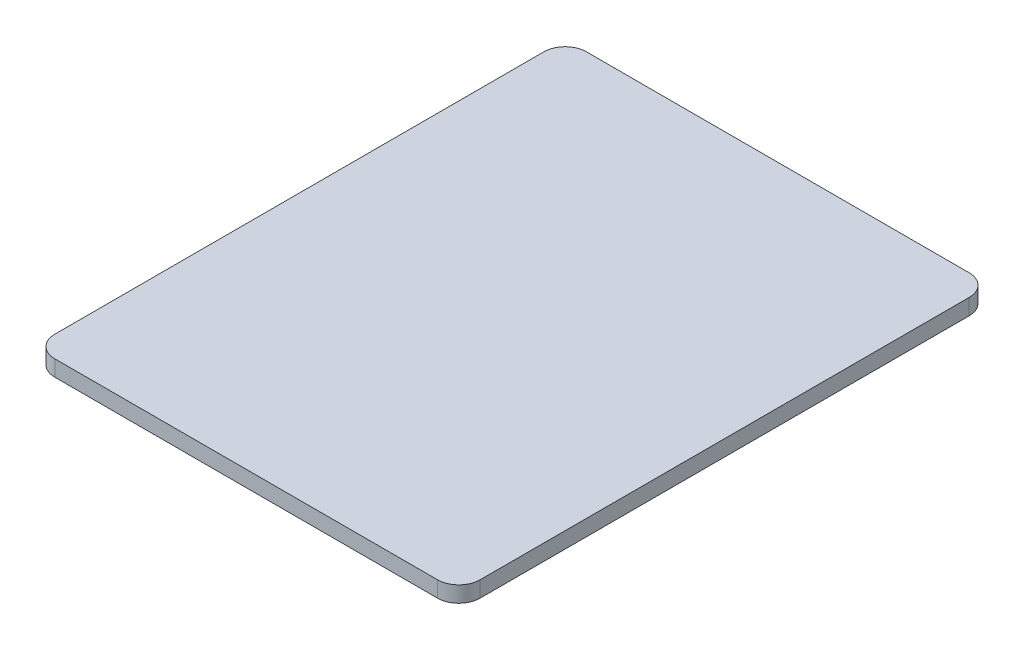
SolidWorks part; units mm, degrees
ref_plane "Спереди" through (0, 0, 0) normal (0, 0, 1) x (1, 0, 0)
ref_plane "Сверху" through (0, 0, 0) normal (0, 1, 0) x (1, 0, 0)
ref_plane "Справа" through (0, 0, 0) normal (1, 0, 0) x (0, 0, -1)
sketch "Эскиз1" plane through (0, 0, 0) normal (0, 1, 0) x (1, 0, 0)
  line L1 (-20, 25) -> (20, 25)
  line L2 (-20, 25) -> (-20, -25)
  line L3 (-20, -25) -> (20, -25)
  line L4 (20, 25) -> (20, -25)
  line L5 (-20, 25) -> (20, -25) construction
  line L6 (-20, -25) -> (20, 25) construction
  point P0 (0, 0)
  dimension "D1" = 50
  dimension "D2" = 40
extrude "Бобышка-Вытянуть1" add sketch "Эскиз1" along normal blind 1.5
fillet "Скругление1" radius 2 4 edges at (-20, 0.75, -25) (20, 0.75, -25) (-20, 0.75, 25) (20, 0.75, 25)
